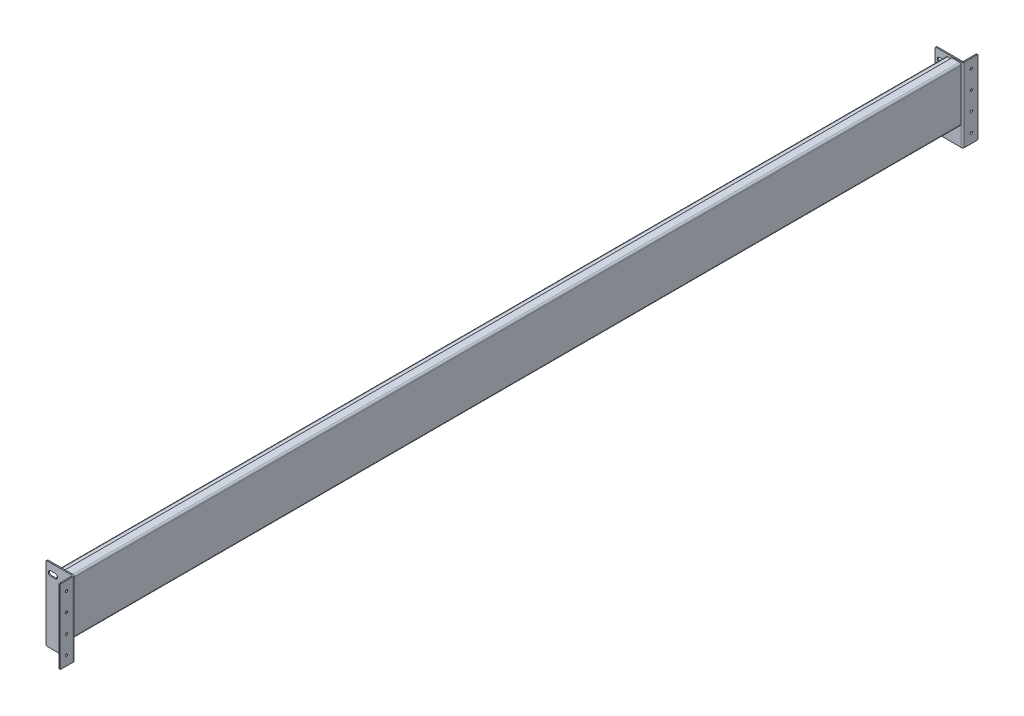
SolidWorks part; units mm, degrees
material "ASTM A36 Steel"
ref_plane "Front Plane" through (0, 0, 0) normal (0, 0, 1) x (1, 0, 0)
ref_plane "Top Plane" through (0, 0, 0) normal (0, 1, 0) x (1, 0, 0)
ref_plane "Right Plane" through (0, 0, 0) normal (1, 0, 0) x (0, 0, -1)
sketch "Sketch1" plane through (0, 0, 0) normal (0, 0, 1) x (1, 0, 0)
  line L0 (6.35, 71.4375) -> (26.9875, 71.4375)
  line L1 (-22.225, -74.6125) -> (26.9875, -74.6125)
  line L2 (28.575, -69.85) -> (28.575, 69.85)
  line L3 (6.35, 74.6125) -> (26.9875, 74.6125)
  line L4 (31.75, -69.85) -> (31.75, 69.85)
  line L5 (-31.75, -74.6125) -> (31.75, 74.6125) construction
  line L6 (-31.75, 74.6125) -> (31.75, -74.6125) construction
  line L7 (0, 0) -> (0, 50000) construction
  line L8 (0, 0) -> (50000, 0) construction
  line L9 (-22.225, -71.4375) -> (26.9875, -71.4375)
  line L10 (6.35, 74.6125) -> (6.35, 71.4375)
  line L11 (-22.225, -71.4375) -> (-22.225, -74.6125)
  arc A0 (26.9875, 74.6125) -> (31.75, 69.85) centre (26.9875, 69.85) cw
  arc A1 (31.75, -69.85) -> (26.9875, -74.6125) centre (26.9875, -69.85) cw
  arc A2 (26.9875, 71.4375) -> (28.575, 69.85) centre (26.9875, 69.85) cw
  arc A3 (28.575, -69.85) -> (26.9875, -71.4375) centre (26.9875, -69.85) cw
  point P0 (0, 0)
  dimension "D3" = 4.7625
  dimension "D1" = 149.225
  dimension "D2" = 63.5
  dimension "D4" = 74.6125
  dimension "D5" = 25.4
  dimension "D6" = 31.75
  dimension "D7" = 22.225
  dimension "D8" = 3.175
extrude "Boss-Extrude1" add sketch "Sketch1" along normal blind 1216.025 and the other way blind 1216.025
sketch "Sketch2" plane through (0, 0, 0) normal (0, 0, 1) x (1, 0, 0)
  line L0 (22.225, 71.4375) -> (-4.7625, 71.4375)
  line L1 (6.35, 71.4375) -> (26.9875, 71.4375) construction
  line L2 (-9.525, 66.675) -> (-9.525, 38.1)
  line L3 (-14.2875, 33.3375) -> (-26.9875, 33.3375)
  line L4 (-31.75, 28.575) -> (-31.75, -66.675)
  line L5 (-26.9875, -71.4375) -> (22.225, -71.4375)
  line L6 (26.9875, -71.4375) -> (-22.225, -71.4375) construction
  line L7 (31.75, -69.85) -> (31.75, 69.85) construction
  line L11 (26.9875, 74.6125) -> (6.35, 74.6125) construction
  line L12 (28.575, 69.85) -> (28.575, -69.85) construction
  line L13 (22.225, 68.2625) -> (-4.7625, 68.2625)
  line L14 (-6.35, 66.675) -> (-6.35, 38.1)
  line L15 (-14.2875, 30.1625) -> (-26.9875, 30.1625)
  line L16 (-28.575, 28.575) -> (-28.575, -66.675)
  line L17 (-26.9875, -68.2625) -> (22.225, -68.2625)
  line L18 (22.225, 68.2625) -> (22.225, 71.4375)
  line L19 (22.225, -68.2625) -> (22.225, -71.4375)
  arc A0 (-26.9875, -71.4375) -> (-31.75, -66.675) centre (-26.9875, -66.675) cw
  arc A1 (-4.7625, 71.4375) -> (-9.525, 66.675) centre (-4.7625, 66.675) ccw
  arc A2 (-9.525, 38.1) -> (-14.2875, 33.3375) centre (-14.2875, 38.1) cw
  arc A3 (-26.9875, 33.3375) -> (-31.75, 28.575) centre (-26.9875, 28.575) ccw
  arc A4 (-4.7625, 68.2625) -> (-6.35, 66.675) centre (-4.7625, 66.675) ccw
  arc A5 (-6.35, 38.1) -> (-14.2875, 30.1625) centre (-14.2875, 38.1) cw
  arc A6 (-26.9875, 30.1625) -> (-28.575, 28.575) centre (-26.9875, 28.575) ccw
  arc A7 (-26.9875, -68.2625) -> (-28.575, -66.675) centre (-26.9875, -66.675) cw
  point P21 (-31.75, -71.4375)
  point P28 (-31.75, 33.3375)
  dimension "D7" = 4.7625
  dimension "D1" = 63.5
  dimension "D2" = 22.225
  dimension "D3" = 41.275
  dimension "D4" = 104.775
  dimension "D5" = 6.35
  dimension "D6" = 6.35
  dimension "D8" = 3.175
extrude "Boss-Extrude2" add sketch "Sketch2" along normal up to surface (1216.025 mm away) and the other way up to surface (1216.025 mm away) separate body up to face at (16.6234, 0, 1216.025) other way up to face at (16.6234, 0, -1216.025)
sketch "Sketch4" plane through (0, -74.6125, 0) normal (0, -1, 0) x (1, 0, 0)
  line L0 (-22.225, 1216.025) -> (26.9875, 1216.025) construction
  line L1 (-39.6875, 1216.025) -> (31.75, 1216.025)
  line L2 (33.3375, 1220.7875) -> (33.3375, 1257.3)
  line L3 (-26.9875, 1216.025) -> (-31.75, 1216.025) construction
  line L4 (-26.9875, 1216.025) -> (-31.75, 1216.025) construction
  line L5 (-39.6875, 1219.2) -> (31.75, 1219.2)
  line L6 (33.3375, 1257.3) -> (36.5125, 1257.3)
  line L7 (-39.6875, 1219.2) -> (-39.6875, 1216.025)
  line L8 (36.5125, 1257.3) -> (36.5125, 1220.7875)
  line L10 (-39.6875, 1216.025) -> (39.0982, 1216.025) construction
  line L11 (36.5125, 1830.3646) -> (36.5125, 1866.9) construction
  line L12 (33.3375, 1828.0786) -> (33.3375, 1866.9) construction
  line L13 (-39.6875, 1219.2) -> (38.5604, 1219.2) construction
  arc A0 (36.5125, 1220.7875) -> (31.75, 1216.025) centre (31.75, 1220.7875) cw
  arc A1 (33.3375, 1220.7875) -> (31.75, 1219.2) centre (31.75, 1220.7875) cw
  arc A2 (36.5125, 1830.3646) -> (39.0982, 1216.025) centre (-67.5809, 1522.7512) cw construction
  arc A3 (33.3375, 1828.0786) -> (38.5604, 1219.2) centre (-67.5809, 1522.7512) cw construction
  point P9 (36.5125, 1825.625)
  point P19 (36.5125, 1825.625)
  dimension "D4" = 76.2
  dimension "D3" = 4.7625
  dimension "D1" = 41.275
  dimension "D2" = 7.9375
  dimension "D5" = 3.175
extrude "Boss-Extrude3" add sketch "Sketch4" along normal blind 50.8 and the other way blind 152.4 separate body
sketch "Sketch5" plane through (33.3375, 0, 0) normal (1, 0, 0) x (0, 0, -1)
  line L0 (-1239.045, 77.7875) -> (-1239.045, -49922.2125) construction
  line L1 (-1257.3, 77.7875) -> (-1257.3, -125.4125) construction
  line L2 (-1257.3, 77.7875) -> (-1220.7875, 77.7875) construction
  circle A0 centre (-1239.045, 52.3875) radius 3.175
  circle A1 centre (-1239.045, 1.5875) radius 3.175
  circle A2 centre (-1239.045, -49.2125) radius 3.175
  circle A3 centre (-1239.045, -100.0125) radius 3.175
  dimension "D6" = 6.35
  dimension "D1" = 18.255
  dimension "D2" = 50.8
  dimension "D3" = 50.8
  dimension "D4" = 50.8
  dimension "D5" = 25.4
extrude "Cut-Extrude1" cut sketch "Sketch5" along normal through all
sketch "Sketch9" plane through (0, 0, 1216.025) normal (0, 0, -1) x (-1, 0, 0)
  line L0 (14.2875, 52.3875) -> (26.9875, 52.3875) construction
  line L1 (14.2875, 58.7375) -> (26.9875, 58.7375)
  line L2 (14.2875, 46.0375) -> (26.9875, 46.0375)
  line L3 (39.6875, 77.7875) -> (-31.75, 77.7875) construction
  line L4 (39.6875, 77.7875) -> (39.6875, -125.4125) construction
  arc A0 (14.2875, 58.7375) -> (14.2875, 46.0375) centre (14.2875, 52.3875) ccw
  arc A1 (26.9875, 46.0375) -> (26.9875, 58.7375) centre (26.9875, 52.3875) ccw
  point P2 (20.6375, 52.3875)
  dimension "D1" = 25.4
  dimension "D2" = 12.7
  dimension "D3" = 12.7
  dimension "D4" = 19.05
extrude "Cut-Extrude2" cut sketch "Sketch9" against normal blind 3.175
sketch "Sketch10" plane through (0, -74.6125, 0) normal (0, -1, 0) x (1, 0, 0)
  line L0 (10.3187, 1196.975) -> (-5.5563, 1196.975) construction
  line L1 (10.3187, 1192.2125) -> (-5.5563, 1192.2125)
  line L2 (10.3187, 1201.7375) -> (-5.5563, 1201.7375)
  line L3 (-22.225, 1216.025) -> (26.9875, 1216.025) construction
  line L4 (2.3812, 1825.625) -> (2.3812, -48174.375) construction
  arc A0 (10.3187, 1192.2125) -> (10.3187, 1201.7375) centre (10.3187, 1196.975) ccw
  arc A1 (-5.5563, 1201.7375) -> (-5.5563, 1192.2125) centre (-5.5563, 1196.975) ccw
  point P2 (2.3812, 1196.975)
  point P11 (2.3812, 1216.025)
  dimension "D1" = 19.05
  dimension "D2" = 15.875
  dimension "D3" = 9.525
extrude "Cut-Extrude3" cut sketch "Sketch10" against normal blind 9.525
mirror "Mirror2" about plane through (0, 0, 0) normal (0, 0, 1) of "Cut-Extrude3"
fillet "Fillet1" radius 2.54 4 edges at (34.925, 77.7875, 1257.3) (34.925, -125.4125, 1257.3) (-39.6875, -125.4125, 1217.6125) (-39.6875, 77.7875, 1217.6125)
mirror "Mirror3" about plane through (0, 0, 0) normal (0, 0, 1) of bodies 119
